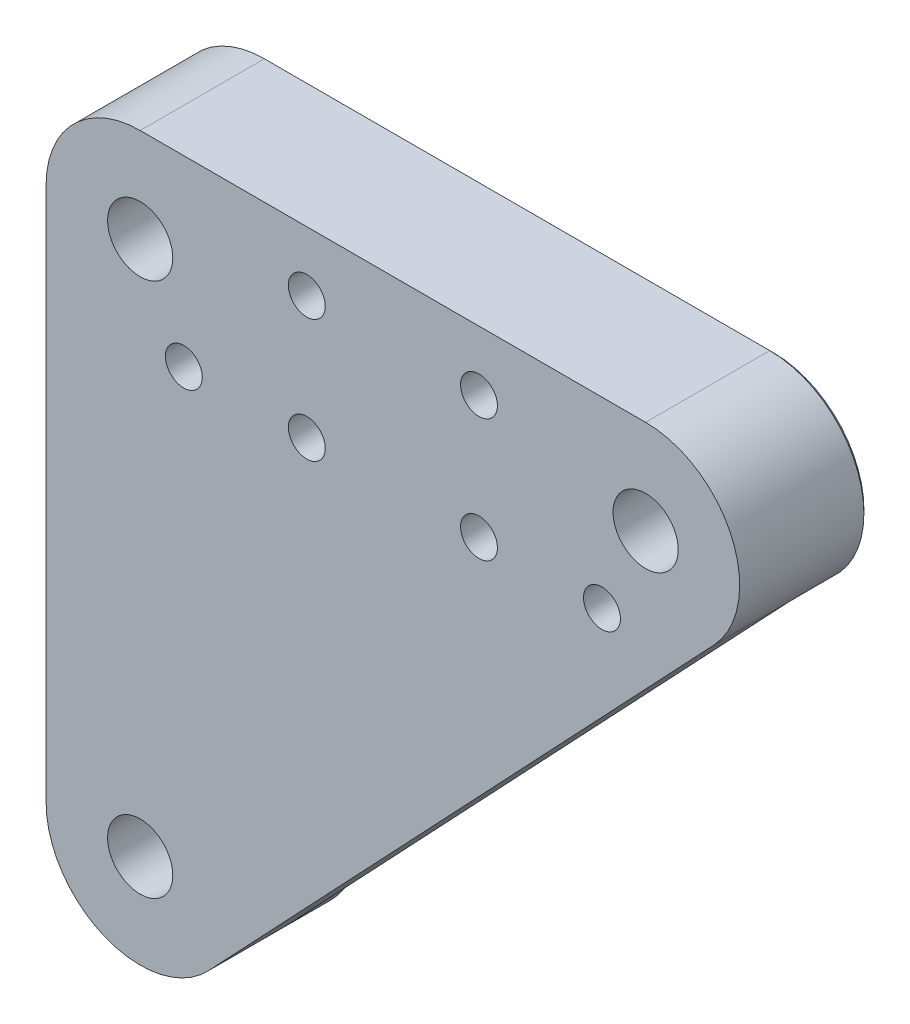
SolidWorks part; units mm, degrees
ref_plane "Front Plane" through (0, 0, 0) normal (0, 0, 1) x (1, 0, 0)
ref_plane "Top Plane" through (0, 0, 0) normal (0, 1, 0) x (1, 0, 0)
ref_plane "Right Plane" through (0, 0, 0) normal (1, 0, 0) x (0, 0, -1)
sketch "Sketch2" plane through (0, 0, 0) normal (0, 0, 1) x (1, 0, 0)
  line L0 (20.55, 0) -> (-20.55, 0) construction
  line L1 (-20.55, 0) -> (-20.55, -43.48) construction
  line L2 (20.55, 7.65) -> (-20.55, 7.65)
  line L3 (-28.2, 0) -> (-28.2, -43.48)
  line L4 (-14.9906, -48.7351) -> (26.1094, -5.2551)
  circle A0 centre (-20.55, 0) radius 2.65
  circle A1 centre (20.55, 0) radius 2.65
  circle A2 centre (-20.55, -43.48) radius 2.65
  circle A3 centre (-20.55, 0) radius 7.65
  circle A4 centre (20.55, 0) radius 7.65
  circle A5 centre (-20.55, -43.48) radius 7.65
  dimension "D1" = 5.3
  dimension "D4" = 15.3
  dimension "D2" = 41.1
  dimension "D3" = 43.48
  dimension "D5" = 20.55
extrude "Boss-Extrude1" add sketch "Sketch2" along normal blind 6.4 contours A5 L4 A4 L2 A3 L3 | A4 A1 | A3 A0 | A5 A2 region at (-6.2287, -15.4373, 0) region at (25.8064, 5.2564, 0) region at (-15.2936, 5.2564, 0) region at (-23.2978, -50.3871, 0)
sketch "Sketch3" plane through (0, 0, 0) normal (0, 0, -1) x (-1, 0, 0)
  line L0 (-20.55, -7.65) -> (20.55, -7.65)
  circle A0 centre (20.55, -43.48) radius 7.65
  circle A1 centre (20.55, 0) radius 7.65
  circle A2 centre (-20.55, 0) radius 7.65
  arc A3 (28.2, 0) -> (20.55, 7.65) centre (20.55, 0) ccw construction
  arc A4 (-20.55, 7.65) -> (-26.1094, -5.2551) centre (-20.55, 0) ccw construction
  arc A5 (14.9906, -48.7351) -> (28.2, -43.48) centre (20.55, -43.48) ccw construction
  arc M2 (28.2, 0) -> (20.55, 7.65) centre (20.55, 0) ccw
  line M3 (20.55, 7.65) -> (-20.55, 7.65)
  arc M4 (-20.55, 7.65) -> (-26.1094, -5.2551) centre (-20.55, 0) ccw
  arc M6 (14.9906, -48.7351) -> (28.2, -43.48) centre (20.55, -43.48) ccw
  circle M7 centre (20.55, 0) radius 2.65
  circle M8 centre (-20.55, 0) radius 2.65
  circle M9 centre (20.55, -43.48) radius 2.65
extrude "Boss-Extrude2" add sketch "Sketch3" along normal blind 4 contours A0 M6 M9 | A1 M2 M7 | A2 L0 A1 M3 | A2 M4 M8 region at (0, 0, 0) region at (23.491, -6.8271, 0) region at (-13.1164, 0, 0) region at (-23.2978, -50.3871, 0)
sketch "Sketch4" plane through (0, 0, -4) normal (0, 0, -1) x (-1, 0, 0)
  line L0 (20.55, 7.65) -> (-20.55, 7.65) construction
  line L1 (-20.55, -7.65) -> (20.55, -7.65) construction
  line L2 (20.55, 7.65) -> (-20.55, 7.65)
  line L3 (-20.55, -7.65) -> (20.55, -7.65)
  circle A0 centre (20.55, -43.48) radius 7.65 construction
  circle A1 centre (-20.55, 0) radius 2.65
  circle A2 centre (-20.55, 0) radius 2.65
  circle A3 centre (20.55, 0) radius 2.65
  circle A4 centre (20.55, 0) radius 2.65
  circle A5 centre (20.55, -43.48) radius 2.65
  circle A6 centre (20.55, -43.48) radius 2.65
  arc A7 (20.55, -7.65) -> (20.55, 7.65) centre (20.55, 0) ccw construction
  arc A8 (-20.55, 7.65) -> (-20.55, -7.65) centre (-20.55, 0) ccw construction
  circle A9 centre (20.55, -43.48) radius 7.65
  arc A10 (20.55, -7.65) -> (20.55, 7.65) centre (20.55, 0) ccw
  arc A11 (-20.55, 7.65) -> (-20.55, -7.65) centre (-20.55, 0) ccw
  circle A12 centre (-20.55, 0) radius 4
  circle A13 centre (20.55, 0) radius 4
  circle A14 centre (20.55, -43.48) radius 4
  circle M4 centre (20.55, 0) radius 2.65
  circle M9 centre (-20.55, 0) radius 2.65
  dimension "D4" = 8
  dimension "D1" = 0
  dimension "D2" = 0
  dimension "D3" = 0
extrude "Boss-Extrude3" add sketch "Sketch4" along normal blind 1 contours A13 M4 | A12 M9 | A14 A6 region at (24.4369, 0, -4) region at (-16.6631, 0, -4) region at (-16.6631, -43.48, -4)
chamfer "Chamfer1" distance 0.3 angle 45 10 edges at (5.5594, -26.9951, 0) (-28.2, -21.74, 0) (-28.2, -43.48, -4) (-24.55, -43.48, -5) (-24.55, 0, -5) (16.55, 0, -5) (0, -7.65, -4) (-28.2, 0, -4) (28.2, 0, -4) (0, 7.65, -4)
sketch "Sketch10" plane through (0, 0, 6.4) normal (0, 0, 1) x (1, 0, 0)
  line L0 (-28.2, 0.785) -> (28.1596, 0.785)
  line L1 (-28.2, 0) -> (-28.2, -43.48) construction
  line L2 (20.55, 7.65) -> (-20.55, 7.65) construction
  line L6 (-28.2, 0) -> (-28.2, -43.48)
  line L7 (-14.9906, -48.7351) -> (26.1094, -5.2551)
  line L8 (20.55, 7.65) -> (-20.55, 7.65)
  line L9 (-28.2, 0) -> (-28.2, -43.48)
  line L10 (-14.9906, -48.7351) -> (26.1094, -5.2551)
  line L11 (20.55, 7.65) -> (-20.55, 7.65)
  line L12 (-28.2, -5.215) -> (28.1596, -5.215)
  line L13 (0, 7.65) -> (0, -8.2542) construction
  line L14 (-7, -7.215) -> (-17, -7.215) construction
  line L15 (-7, -7.215) -> (-7, 2.785) construction
  arc A3 (-28.2, -43.48) -> (-14.9906, -48.7351) centre (-20.55, -43.48) ccw
  arc A4 (26.1094, -5.2551) -> (20.55, 7.65) centre (20.55, 0) ccw
  arc A5 (-20.55, 7.65) -> (-28.2, 0) centre (-20.55, 0) ccw
  arc A6 (-28.2, -43.48) -> (-14.9906, -48.7351) centre (-20.55, -43.48) ccw
  arc A7 (26.1094, -5.2551) -> (20.55, 7.65) centre (20.55, 0) ccw
  arc A8 (-20.55, 7.65) -> (-28.2, 0) centre (-20.55, 0) ccw
  circle A9 centre (-7, 2.785) radius 1.5
  circle A10 centre (-17, -7.215) radius 1.5
  circle A11 centre (-7, -7.215) radius 1.5
  circle A12 centre (17, -7.215) radius 1.5
  circle A13 centre (7, -7.215) radius 1.5
  circle A14 centre (7, 2.785) radius 1.5
  dimension "D6" = 3
  dimension "D1" = 6.865
  dimension "D4" = 10
  dimension "D5" = 10
  dimension "D7" = 2
  dimension "D8" = 7
  dimension "D2" = 0
  dimension "D3" = 6
extrude "Cut-Extrude2" cut sketch "Sketch10" against normal through all contours A9 | A10 | A11 | A14 | A13 | A12 region at (-7, 2.785, 6.4) region at (-17, -7.215, 6.4) region at (-7, -7.215, 6.4) region at (17, -7.215, 6.4) region at (7, -7.215, 6.4) region at (7, 2.785, 6.4)
